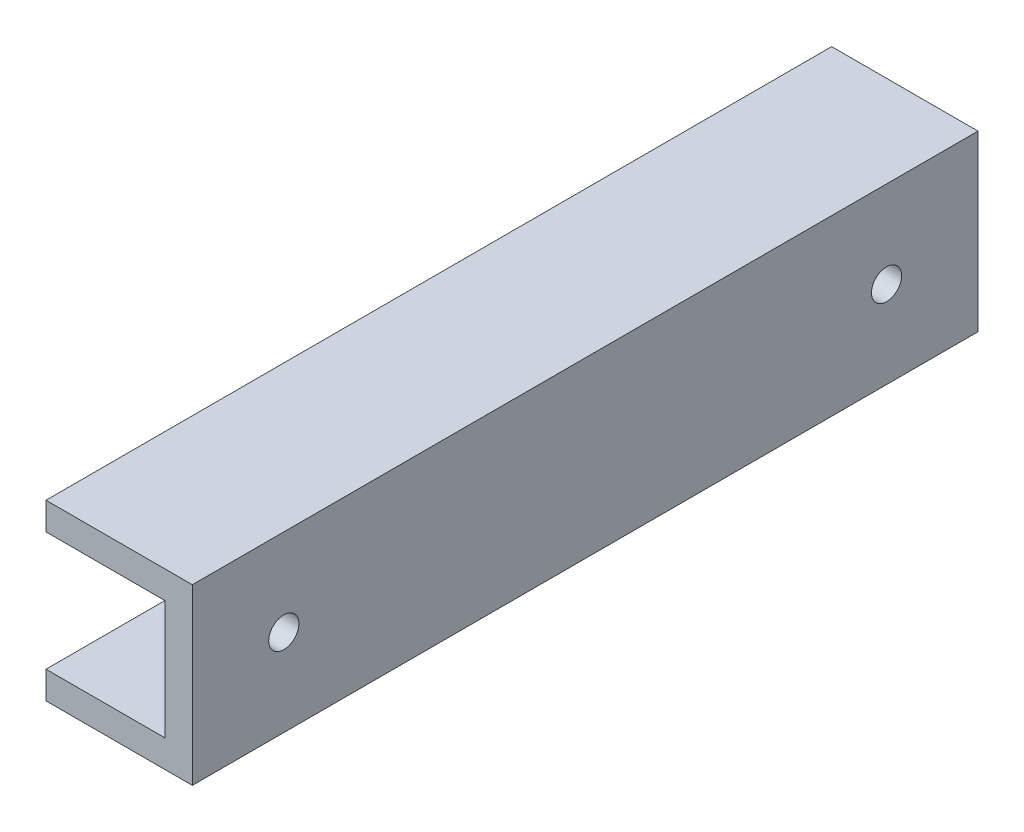
SolidWorks part; units mm, degrees
ref_plane "前视基准面" through (0, 0, 0) normal (0, 0, 1) x (1, 0, 0)
ref_plane "上视基准面" through (0, 0, 0) normal (0, 1, 0) x (1, 0, 0)
ref_plane "右视基准面" through (0, 0, 0) normal (1, 0, 0) x (0, 0, -1)
sketch "草图1" plane through (0, 0, 0) normal (0, 0, 1) x (1, 0, 0)
  line L1 (0, 0) -> (13, 0)
  line L2 (0, 0) -> (0, 13)
  line L3 (0, 13) -> (13, 13)
  line L4 (13, 0) -> (13, 13)
  dimension "D1" = 13
  dimension "D2" = 13
extrude "拉伸-薄壁1" add sketch "草图1" along normal blind 85.9 thin thin type one direction wall 3
sketch "草图2" plane through (-3, 0, 0) normal (-1, 0, 0) x (0, 0, 1)
  line L0 (0, 16) -> (0, -3) construction
  line L1 (85.9, 16) -> (85.9, -3) construction
  circle A0 centre (10, 6.5) radius 1.65
  circle A1 centre (75.9, 6.5) radius 1.65
  dimension "D1" = 3.3
  dimension "D2" = 3.3
  dimension "D3" = 10
  dimension "D4" = 10
extrude "切除-拉伸1" cut sketch "草图2" against normal blind 30
sketch "草图3" plane through (-3, 0, 0) normal (-1, 0, 0) x (0, 0, 1)
  line L1 (-5.2954, 23.3125) -> (111.6198, 23.3125)
  line L2 (-5.2954, 23.3125) -> (-5.2954, -22.907)
  line L3 (-5.2954, -22.907) -> (111.6198, -22.907)
  line L4 (111.6198, 23.3125) -> (111.6198, -22.907)
extrude "切除-拉伸2" cut sketch "草图3" against normal blind 3
sketch "草图4" plane through (13, 0, 0) normal (-1, 0, 0) x (0, 0, 1)
  line L0 (85.9, 13) -> (0, 13) construction
  line L1 (23, 13) -> (28, 13)
  line L2 (23, 13) -> (23, 0)
  line L3 (23, 0) -> (28, 0)
  line L4 (28, 13) -> (28, 0)
  line L5 (85.9, 0) -> (0, 0) construction
  line L6 (85.9, 13) -> (0, 13) construction
  line L7 (57.9, 13) -> (62.9, 13)
  line L8 (57.9, 13) -> (57.9, 0)
  line L9 (57.9, 0) -> (62.9, 0)
  line L10 (62.9, 13) -> (62.9, 0)
  line L11 (85.9, 0) -> (0, 0) construction
  line L12 (85.9, 0) -> (85.9, 13) construction
  line L13 (0, 0) -> (0, 13) construction
  dimension "D1" = 23
  dimension "D2" = 23
  dimension "D3" = 5
  dimension "D4" = 5
extrude "凸台-拉伸1" add sketch "草图4" along normal blind 10
sketch "草图5" plane through (13, 0, 0) normal (-1, 0, 0) x (0, 0, 1)
  line L0 (28, 0) -> (28, 13) construction
  line L1 (28, 9) -> (57.9, 9)
  line L2 (28, 9) -> (28, 4)
  line L3 (28, 4) -> (57.9, 4)
  line L4 (57.9, 9) -> (57.9, 4)
  line L5 (57.9, 13) -> (57.9, 0) construction
  line L6 (57.9, 0) -> (28, 0) construction
  dimension "D1" = 5
  dimension "D2" = 4
extrude "凸台-拉伸2" add sketch "草图5" along normal blind 10
sketch "草图6" plane through (13, 0, 0) normal (-1, 0, 0) x (0, 0, 1)
  line L1 (23, 13) -> (62.9, 13)
  line L2 (23, 13) -> (23, 0)
  line L3 (23, 0) -> (62.9, 0)
  line L4 (62.9, 13) -> (62.9, 0)
extrude "凸台-拉伸3" add sketch "草图6" along normal blind 10
sketch "草图7" plane through (3, 0, 0) normal (-1, 0, 0) x (0, 0, 1)
  line L0 (23, 13) -> (23, 0) construction
  line L1 (23, 9) -> (62.9, 9)
  line L2 (23, 9) -> (23, 4)
  line L3 (23, 4) -> (62.9, 4)
  line L4 (62.9, 9) -> (62.9, 4)
  line L5 (62.9, 0) -> (62.9, 13) construction
  line L6 (85.9, 13) -> (0, 13) construction
  dimension "D1" = 5
  dimension "D2" = 4
extrude "凸台-拉伸4" [suppressed] add sketch "草图7" along normal blind 3
sketch "草图8" plane through (3, 0, 0) normal (-1, 0, 0) x (0, 0, 1)
  line L0 (23, 13) -> (23, 0) construction
  line L1 (23, 9) -> (62.9, 9)
  line L2 (23, 9) -> (23, 4)
  line L3 (23, 4) -> (62.9, 4)
  line L4 (62.9, 9) -> (62.9, 4)
  line L5 (62.9, 0) -> (62.9, 13) construction
  line L6 (85.9, 13) -> (0, 13) construction
  dimension "D1" = 5
  dimension "D2" = 4
extrude "切除-拉伸3" cut sketch "草图8" against normal blind 3
chamfer "倒角1" distance 3 angle 45 2 edges at (6, 6.5, 62.9) (6, 6.5, 23)
chamfer "倒角2" distance 4 angle 45 2 edges at (13, 6.5, 62.9) (13, 6.5, 23)
